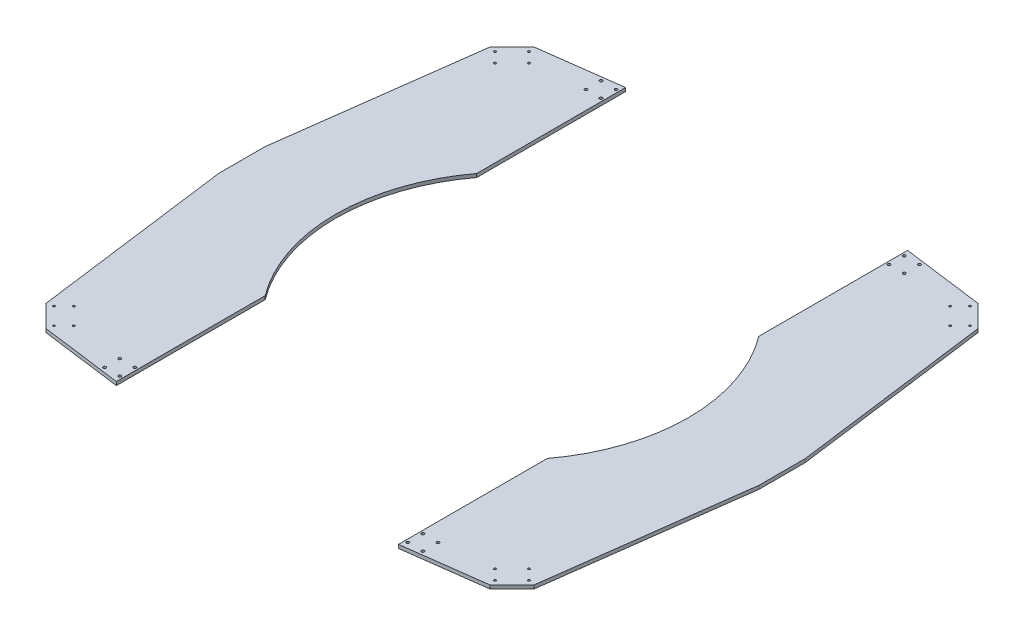
SolidWorks part; units mm, degrees
ref_plane "前视基准面" through (0, 0, 0) normal (0, 0, 1) x (1, 0, 0)
ref_plane "上视基准面" through (0, 0, 0) normal (0, 1, 0) x (1, 0, 0)
ref_plane "右视基准面" through (0, 0, 0) normal (1, 0, 0) x (0, 0, -1)
other "Configuration Table"
sketch "草图1" plane through (0, 0, 0) normal (0, 1, 0) x (1, 0, 0)
  line L0 (-314.9222, 345.9222) -> (-345.9222, 314.9222)
  line L5 (325, -325) -> (-325, 325) construction
  line L6 (325, 325) -> (-325, -325) construction
  line L7 (0, 325) -> (0, -325) construction
  line L8 (-325, 0) -> (325, 0) construction
  line L9 (314.9222, 345.9222) -> (32.7201, 383.0748)
  line L10 (314.9222, 345.9222) -> (345.9222, 314.9222)
  line L12 (-314.9222, 345.9222) -> (-32.7201, 383.0748)
  line L13 (0, 325) -> (0, 399.6983)
  line L14 (-32.7201, 383.0748) -> (32.7201, 383.0748)
  line L15 (314.9222, -345.9222) -> (32.7201, -383.0748)
  line L16 (-32.7201, -383.0748) -> (32.7201, -383.0748)
  line L17 (-314.9222, -345.9222) -> (-32.7201, -383.0748)
  line L18 (-314.9222, -345.9222) -> (-345.9222, -314.9222)
  line L19 (-345.9222, 314.9222) -> (-383.0748, 32.7201)
  line L20 (-383.0748, -32.7201) -> (-383.0748, 32.7201)
  line L21 (-345.9222, -314.9222) -> (-383.0748, -32.7201)
  line L22 (-345.9222, -314.9222) -> (-314.9222, -345.9222)
  line L23 (345.9222, -314.9222) -> (314.9222, -345.9222)
  line L24 (345.9222, -314.9222) -> (383.0748, -32.7201)
  line L25 (383.0748, 32.7201) -> (383.0748, -32.7201)
  line L26 (345.9222, 314.9222) -> (383.0748, 32.7201)
  circle A5 centre (0, 0) radius 250
  circle A6 centre (298.6024, 322.644) radius 1.5
  circle A7 centre (312.7445, 336.7861) radius 1.5
  circle A8 centre (336.7861, 312.7445) radius 1.5
  circle A9 centre (322.644, 298.6024) radius 1.5
  circle A10 centre (298.6024, -322.644) radius 1.5
  circle A11 centre (312.7445, -336.7861) radius 1.5
  circle A12 centre (322.644, -298.6024) radius 1.5
  circle A13 centre (336.7861, -312.7445) radius 1.5
  circle A14 centre (-322.644, -298.6024) radius 1.5
  circle A15 centre (-336.7861, -312.7445) radius 1.5
  circle A16 centre (-298.6024, -322.644) radius 1.5
  circle A17 centre (-312.7445, -336.7861) radius 1.5
  circle A18 centre (-298.6024, 322.644) radius 1.5
  circle A19 centre (-312.7445, 336.7861) radius 1.5
  circle A20 centre (-322.644, 298.6024) radius 1.5
  circle A21 centre (-336.7861, 312.7445) radius 1.5
  point P0 (0, 0)
  point P13 (0, 383.0748)
  point P24 (-330.4222, -330.4222)
  point P75 (0, 0)
  dimension "D8" = 500
  dimension "D5" = 4
  dimension "D1" = 650
  dimension "D2" = 650
  dimension "D3" = 31
  dimension "D4" = 142.5
extrude "凸台-拉伸2" add sketch "草图1" along normal blind 5 contours L26 L10 L9 L14 L12 L0 L19 L20 L21 L18 L17 L16 L15 L23 L24 L25 | A13 L22 | L22 | A13 L18 region at (-172.4069, 0, -353.7562)
sketch "草图2" plane through (0, 5, 0) normal (0, 1, 0) x (1, 0, 0)
  line L0 (0, 0) -> (-330.4222, -330.4222) construction
  line L1 (0, 383.0748) -> (0, -383.0748)
  line L2 (-32.7201, 383.0748) -> (32.7201, 383.0748) construction
  line L3 (-32.7201, -383.0748) -> (32.7201, -383.0748) construction
  line L4 (-200, 361.052) -> (-200, -361.052)
  line L5 (-314.9222, 345.9222) -> (-32.7201, 383.0748) construction
  line L6 (-314.9222, -345.9222) -> (-32.7201, -383.0748) construction
  line L7 (200, 361.052) -> (200, -361.052)
  line L8 (314.9222, 345.9222) -> (32.7201, 383.0748) construction
  line L9 (314.9222, -345.9222) -> (32.7201, -383.0748) construction
  line L10 (-200, 361.052) -> (-200, 484.7149)
  line L11 (-200, 484.7149) -> (200, 484.7149)
  line L12 (200, 484.7149) -> (200, 361.052)
  line L13 (-200, -361.052) -> (-200, -418.819)
  line L14 (-200, -418.819) -> (200, -418.819)
  line L15 (200, -418.819) -> (200, -361.052)
  line M2 (32.7201, 383.0748) -> (-32.7201, 383.0748)
  line M3 (-32.7201, 383.0748) -> (-314.9222, 345.9222)
  line M9 (-314.9222, -345.9222) -> (-32.7201, -383.0748)
  line M10 (-32.7201, -383.0748) -> (32.7201, -383.0748)
  line M11 (32.7201, -383.0748) -> (314.9222, -345.9222)
  line M17 (314.9222, 345.9222) -> (32.7201, 383.0748)
  circle M27 centre (0, 0) radius 250
  dimension "D1" = 200
  dimension "D2" = 200
extrude "切除-拉伸1" cut sketch "草图2" against normal blind 122 and the other way through all contours L4 L1 M3 M27 M2 | L7 L1 M17 M2 M27 | L7 L1 M27 M10 M11 | L4 L1 M27 M9 M10 | L0 L4 M27 region at (-105.9786, 5, 296.6115) region at (-192.3556, 5, 175.9086) region at (-107.5653, 5, -294.3941) region at (107.5653, 5, -294.3941) region at (107.5653, 5, 294.3941)
sketch "草图3" plane through (0, 0, 0) normal (0, -1, 0) x (-1, 0, 0)
  circle A0 centre (225.7527, -352.0225) radius 2
  circle A1 centre (204.2473, -352.0225) radius 2
  circle A2 centre (225.7527, -330.517) radius 2
  circle A3 centre (204.2473, -330.517) radius 2
  point P2 (225.7527, -352.0225)
  point P6 (204.2473, -352.0225)
  point P10 (225.7527, -330.517)
  point P14 (204.2473, -330.517)
extrude "切除-拉伸2" cut sketch "草图3" along normal through all and the other way blind 39 contours A0 | A1 | A2 | A3
sketch "草图4" plane through (0, 5, 0) normal (0, 1, 0) x (1, 0, 0)
  line L0 (-225.7527, 352.0186) -> (-204.2473, 352.0186)
  line L1 (-215, 352.0186) -> (-215, 326.2032)
  circle A0 centre (-225.7527, 352.0186) radius 2
  circle A1 centre (-204.2473, 352.0186) radius 2
  circle A2 centre (-225.7527, 330.5131) radius 2
  circle A3 centre (-204.2473, 330.5131) radius 2
  circle A4 centre (204.2473, 330.5131) radius 2
  circle A5 centre (225.7527, 330.5131) radius 2
  circle A6 centre (204.2473, 352.0186) radius 2
  circle A7 centre (225.7527, 352.0186) radius 2
  circle A8 centre (204.2473, -352.0225) radius 2
  circle A9 centre (225.7527, -352.0225) radius 2
  circle A10 centre (204.2473, -330.517) radius 2
  circle A11 centre (225.7527, -330.517) radius 2
  point P10 (-225.7527, 330.5131)
  point P14 (-204.2473, 330.5131)
  point P18 (-25.7146, 257.3466)
  point P19 (124.5338, 326.2032)
  point P20 (204.2473, 330.5131)
  point P24 (225.7527, 330.5131)
  point P28 (204.2473, 352.0186)
  point P32 (225.7527, 352.0186)
  point P36 (204.2473, -352.0225)
  point P40 (225.7527, -352.0225)
  point P44 (204.2473, -330.517)
  point P48 (225.7527, -330.517)
  point P50 (0, 0)
  dimension "D1" = 4
extrude "切除-拉伸3" cut sketch "草图4" against normal through all and the other way blind 20 contours A8 | A9 | A11 | A4 | A6 | A5 | A7 | A1 | A0 | A2 | A3 | A10 region at (-204.2473, 5, -353.962) region at (-227.6962, 5, -352.0186) region at (-225.7527, 5, -330.5131) region at (-204.2473, 5, -330.5131) region at (204.2473, 5, -330.5131) region at (225.7527, 5, -330.5131) region at (204.2473, 5, -352.0186) region at (225.7527, 5, -352.0186) region at (204.2473, 5, 352.0225) region at (225.7527, 5, 352.0225) region at (225.7527, 5, 330.517)
